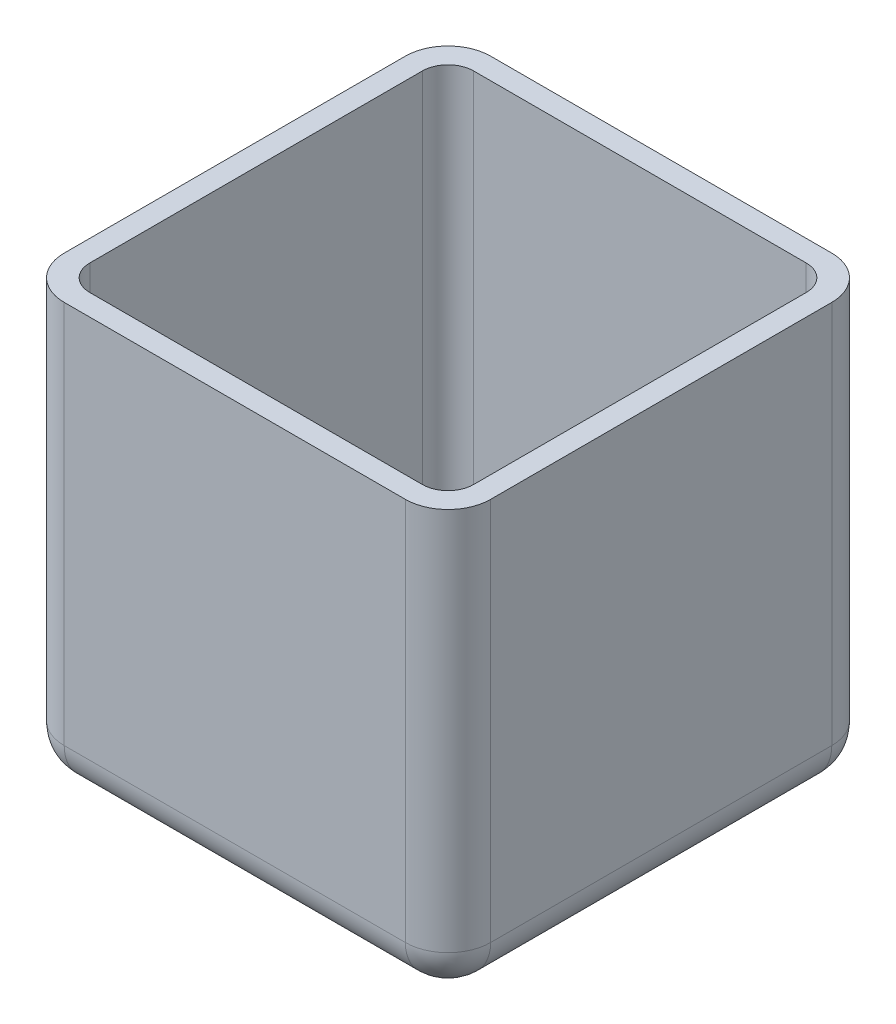
SolidWorks part; units mm, degrees
ref_plane "Front Plane" through (0, 0, 0) normal (0, 0, 1) x (1, 0, 0)
ref_plane "Top Plane" through (0, 0, 0) normal (0, 1, 0) x (1, 0, 0)
ref_plane "Right Plane" through (0, 0, 0) normal (1, 0, 0) x (0, 0, -1)
sketch "Sketch1" plane through (0, 0, 0) normal (0, 1, 0) x (1, 0, 0)
  line L1 (-25, -25) -> (25, -25)
  line L2 (-25, -25) -> (-25, 25)
  line L3 (-25, 25) -> (25, 25)
  line L4 (25, -25) -> (25, 25)
  line L5 (-25, -25) -> (25, 25) construction
  line L6 (-25, 25) -> (25, -25) construction
  point P0 (0, 0)
  dimension "D1" = 50
  dimension "D2" = 50
extrude "Boss-Extrude1" add sketch "Sketch1" along normal blind 50
sketch "Sketch2" plane through (0, 50, 0) normal (0, 1, 0) x (1, 0, 0)
  line L1 (-22.5, -22.5) -> (22.5, -22.5)
  line L2 (-22.5, -22.5) -> (-22.5, 22.5)
  line L3 (-22.5, 22.5) -> (22.5, 22.5)
  line L4 (22.5, -22.5) -> (22.5, 22.5)
  line L5 (-22.5, -22.5) -> (22.5, 22.5) construction
  line L6 (-22.5, 22.5) -> (22.5, -22.5) construction
  point P0 (0, 0)
  dimension "D1" = 45
  dimension "D2" = 45
extrude "Cut-Extrude1" cut sketch "Sketch2" against normal offset from surface (45 mm away) 5 up to face at (0, 0, 0)
fillet "Fillet2" radius 5 8 edges at (-25, 25, -25) (-25, 0, 0) (0, 0, -25) (25, 25, -25) (25, 0, 0) (0, 0, 25) (-25, 25, 25) (25, 25, 25)
fillet "Fillet3" radius 3 4 edges at (-22.5, 27.5, 22.5) (-22.5, 27.5, -22.5) (22.5, 27.5, 22.5) (22.5, 27.5, -22.5)
